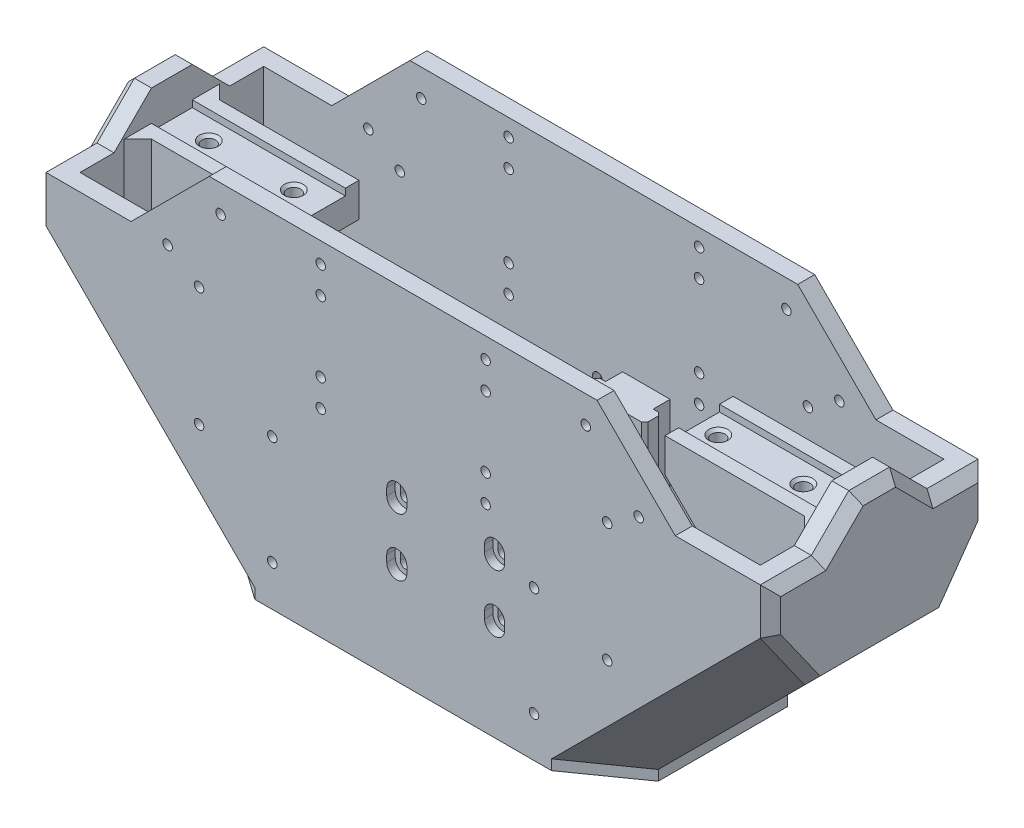
SolidWorks part; units mm, degrees
ref_plane "Front Plane" through (0, 0, 0) normal (0, 0, 1) x (1, 0, 0)
ref_plane "Top Plane" through (0, 0, 0) normal (0, 1, 0) x (1, 0, 0)
ref_plane "Right Plane" through (0, 0, 0) normal (1, 0, 0) x (0, 0, -1)
sketch "Sketch1" plane through (0, 0, 0) normal (0, 1, 0) x (1, 0, 0)
  line L1 (-100, -27) -> (100, -27)
  line L2 (-100, -27) -> (-100, 27)
  line L3 (-100, 27) -> (100, 27)
  line L4 (100, -27) -> (100, 27)
  line L5 (-100, -27) -> (100, 27) construction
  line L6 (-100, 27) -> (100, -27) construction
  point P0 (0, 0)
  dimension "D1" = 200
  dimension "D2" = 54
extrude "Boss-Extrude1" add sketch "Sketch1" along normal blind 70
shell "Shell1" thickness 5
sketch "Sketch2" plane through (105, 0, 0) normal (1, 0, 0) x (0, 0, -1)
  line L0 (-17, 70) -> (-6, 81)
  line L1 (-32, 70) -> (32, 70) construction
  line L2 (-6, 81) -> (6, 81)
  line L3 (6, 81) -> (17, 70)
  line L4 (17, 70) -> (-17, 70)
  line L5 (0, 81) -> (0, 75) construction
  dimension "D1" = 11
  dimension "D2" = 45
  dimension "D3" = 45
  dimension "D4" = 12
extrude "Boss-Extrude2" add sketch "Sketch2" against normal blind 5
sketch "Sketch4" plane through (0, 0, -32) normal (0, 0, -1) x (-1, 0, 0)
  line L0 (-80, 70) -> (-57, 93)
  line L1 (-105, 70) -> (105, 70) construction
  line L2 (-57, 93) -> (57, 93)
  line L3 (57, 93) -> (80, 70)
  line L4 (80, 70) -> (-80, 70)
  line L5 (0, 93) -> (0, 70) construction
  line L6 (-105, 70) -> (-105, -5) construction
  dimension "D1" = 23
  dimension "D2" = 25
  dimension "D3" = 45
extrude "Boss-Extrude3" add sketch "Sketch4" against normal blind 5
sketch "Sketch3" plane through (0, 0, -32) normal (0, 0, -1) x (-1, 0, 0)
  line L1 (-28, 56) -> (28, 56) construction
  line L2 (-28, 56) -> (-28, 88) construction
  line L3 (-28, 88) -> (28, 88) construction
  line L4 (28, 56) -> (28, 88) construction
  line L5 (-28, 56) -> (28, 88) construction
  line L6 (-28, 88) -> (28, 56) construction
  line L7 (57, 93) -> (-57, 93) construction
  circle A0 centre (-28, 88) radius 1.4
  circle A1 centre (-28, 56) radius 1.4
  circle A2 centre (28, 88) radius 1.4
  circle A3 centre (28, 56) radius 1.4
  point P0 (0, 72)
  dimension "D1" = 2.8
  dimension "D2" = 56
  dimension "D3" = 32
  dimension "D4" = 5
extrude "Cut-Extrude1" cut sketch "Sketch3" against normal blind 6
mirror "Mirror4" about plane through (0, 0, 0) normal (0, 0, 1) of "Boss-Extrude3"
mirror "Mirror5" about plane through (0, 0, 0) normal (1, 0, 0) of "Boss-Extrude2"
sketch "Sketch5" plane through (0, 0, 0) normal (0, 0, 1) x (1, 0, 0)
  line L0 (-100, 70) -> (-55, 70)
  line L1 (-55, 70) -> (-55, 62)
  line L2 (-55, 62) -> (-100, 17)
  line L4 (-100, 17) -> (-100, 70)
  line L5 (-100, 81) -> (-100, 70) construction
  line L6 (-105, 70) -> (-80, 70) construction
  dimension "D1" = 45
  dimension "D2" = 8
  dimension "D3" = 45
extrude "Boss-Extrude4" add sketch "Sketch5" along normal mid plane 20
sketch "Sketch9" plane through (0, 70, 0) normal (0, 1, 0) x (1, 0, 0)
  line L4 (-55, 10) -> (-100, 10)
  line L5 (-100, 10) -> (-100, -10)
  line L6 (-100, -10) -> (-55, -10)
  line L7 (-55, -10) -> (-55, 10)
  line L8 (-55, 10) -> (-100, 10)
  line L10 (-100, -10) -> (-55, -10)
  line L11 (-55, -10) -> (-55, 10)
  line L13 (-100, 10) -> (-100, -10)
  dimension "D1" = 0
extrude "Boss-Extrude6" add sketch "Sketch9" along normal blind 2
sketch "Sketch10" plane through (-100, 0, 0) normal (1, 0, 0) x (0, 0, -1)
  line L0 (-10, 72) -> (10, 72) construction
  line L1 (-6, 72) -> (6, 72)
  line L2 (-6, 72) -> (-6, 70)
  line L3 (-6, 70) -> (6, 70)
  line L4 (6, 72) -> (6, 70)
  line L5 (-6, 72) -> (6, 70) construction
  line L6 (-6, 70) -> (6, 72) construction
  point P0 (0, 71)
  dimension "D1" = 2
  dimension "D2" = 12
extrude "Cut-Extrude2" cut sketch "Sketch10" along normal up to next
mirror "Mirror24" about plane through (0, 0, 0) normal (1, 0, 0) of "Boss-Extrude6", "Boss-Extrude4", "Cut-Extrude2"
chamfer "Chamfer3" distance 40 angle 45 2 edges at (100, 0, 0) (-100, 0, 0)
chamfer "Chamfer5" distance 43 angle 45 2 edges at (105, -5, 0) (-105, -5, 0)
chamfer "Chamfer11" distance 10 angle 45 4 edges at (80, 20, 27) (80, 20, -27) (-80, 20, -27) (-80, 20, 27)
chamfer "Chamfer12" distance 13 angle 45 4 edges at (83.5, 16.5, -32) (83.5, 16.5, 32) (-83.5, 16.5, -32) (-83.5, 16.5, 32)
chamfer "Chamfer13" distance 4 angle 45 4 edges at (-100, 56, 10) (-100, 56, -10) (100, 56, -10) (100, 56, 10)
sketch "Sketch16" plane through (105, 0, 0) normal (1, 0, 0) x (0, 0, -1)
  line L10 (-19, 38) -> (19, 38)
  line L11 (19, 38) -> (32, 56.3848)
  line L12 (32, 56.3848) -> (32, 70)
  line L13 (32, 70) -> (17, 70)
  line L14 (17, 70) -> (6, 81)
  line L15 (6, 81) -> (-6, 81)
  line L16 (-6, 81) -> (-17, 70)
  line L17 (-17, 70) -> (-32, 70)
  line L18 (-32, 70) -> (-32, 56.3848)
  line L19 (-32, 56.3848) -> (-19, 38)
  line L20 (-19, 38) -> (19, 38)
  line L21 (19, 38) -> (32, 56.3848)
  line L22 (32, 56.3848) -> (32, 70)
  line L23 (32, 70) -> (17, 70)
  line L24 (17, 70) -> (6, 81)
  line L25 (6, 81) -> (-6, 81)
  line L26 (-6, 81) -> (-17, 70)
  line L27 (-17, 70) -> (-32, 70)
  line L28 (-32, 70) -> (-32, 56.3848)
  line L29 (-32, 56.3848) -> (-19, 38)
  dimension "D1" = 0
extrude "Boss-Extrude10" add sketch "Sketch16" along normal blind 3
chamfer "Chamfer14" distance 3 angle 45 10 edges at (108, 63.1924, 32) (108, 70, 24.5) (108, 75.5, 11.5) (108, 81, 0) (108, 75.5, -11.5) (108, 70, -24.5) (108, 63.1924, -32) (108, 47.1924, -25.5) (108, 38, 0) (108, 47.1924, 25.5)
mirror "Mirror28" about plane through (0, 0, 0) normal (1, 0, 0) of "Chamfer14", "Boss-Extrude10"
sketch "Sketch17" plane through (0, 0, 0) normal (0, 1, 0) x (1, 0, 0)
  line L0 (-57, -27) -> (57, -27) construction
  line L1 (5.5, -27) -> (19.5, -27)
  line L2 (5.5, -27) -> (5.5, -22)
  line L3 (5.5, -22) -> (19.5, -22)
  line L4 (19.5, -27) -> (19.5, -22)
  line L5 (5.5, -27) -> (19.5, -22) construction
  line L6 (5.5, -22) -> (19.5, -27) construction
  line L7 (3, -22) -> (22, -22)
  line L8 (3, -22) -> (3, -17)
  line L9 (3, -17) -> (22, -17)
  line L10 (22, -22) -> (22, -17)
  line L11 (3, -22) -> (22, -17) construction
  line L12 (3, -17) -> (22, -22) construction
  point P0 (12.5, -24.5)
  point P5 (12.5, -19.5)
  line M10 (-45.8579, -27) -> (45.8579, -27)
  dimension "D1" = 19
  dimension "D2" = 14
  dimension "D3" = 5
  dimension "D4" = 12.5
extrude "Boss-Extrude11" add sketch "Sketch17" along normal blind 45 contours L7 L10 L9 L8 L3 | L4 L3 L2 M10
sketch "Sketch20" plane through (0, 0, 0) normal (0, 1, 0) x (1, 0, 0)
  line L0 (22, -22) -> (22, -17) construction
  line L1 (3, -17) -> (22, -17)
  line L2 (3, -17) -> (3, -12)
  line L3 (3, -12) -> (22, -12)
  line L4 (22, -17) -> (22, -12)
  dimension "D1" = 5
extrude "Boss-Extrude14" add sketch "Sketch20" along normal blind 8
mirror "Mirror29" about plane through (0, 0, 0) normal (0, 0, 1) of "Boss-Extrude14", "Boss-Extrude11"
sketch "Sketch22" plane through (0, 0, -27) normal (0, 0, 1) x (1, 0, 0)
  line L0 (5.5, 0) -> (-45.8579, 0) construction
  line L1 (-1.875, 21.8) -> (26.875, 21.8) construction
  line L2 (-1.875, 21.8) -> (-1.875, 38.8) construction
  line L3 (-1.875, 38.8) -> (26.875, 38.8) construction
  line L4 (26.875, 21.8) -> (26.875, 38.8) construction
  line L5 (-1.875, 21.8) -> (26.875, 38.8) construction
  line L6 (-1.875, 38.8) -> (26.875, 21.8) construction
  line L7 (3, 45) -> (22, 45) construction
  line L8 (-1.875, 37.8) -> (-1.875, 39.8) construction
  line L9 (-3.325, 37.8) -> (-3.325, 39.8)
  line L10 (-0.425, 37.8) -> (-0.425, 39.8)
  line L11 (12.5, 38.8) -> (12.5, 30.3) construction
  line L12 (12.5, 30.3) -> (-1.875, 30.3) construction
  line L13 (26.875, 37.8) -> (26.875, 39.8) construction
  line L14 (28.325, 37.8) -> (28.325, 39.8)
  line L15 (25.425, 37.8) -> (25.425, 39.8)
  line L16 (-1.875, 22.8) -> (-1.875, 20.8) construction
  line L17 (-3.325, 22.8) -> (-3.325, 20.8)
  line L18 (-0.425, 22.8) -> (-0.425, 20.8)
  line L19 (26.875, 22.8) -> (26.875, 20.8) construction
  line L20 (28.325, 22.8) -> (28.325, 20.8)
  line L21 (25.425, 22.8) -> (25.425, 20.8)
  arc A4 (-3.325, 37.8) -> (-0.425, 37.8) centre (-1.875, 37.8) ccw
  arc A5 (-0.425, 39.8) -> (-3.325, 39.8) centre (-1.875, 39.8) ccw
  arc A6 (28.325, 37.8) -> (25.425, 37.8) centre (26.875, 37.8) cw
  arc A7 (25.425, 39.8) -> (28.325, 39.8) centre (26.875, 39.8) cw
  arc A8 (-3.325, 22.8) -> (-0.425, 22.8) centre (-1.875, 22.8) cw
  arc A9 (-0.425, 20.8) -> (-3.325, 20.8) centre (-1.875, 20.8) cw
  arc A10 (28.325, 22.8) -> (25.425, 22.8) centre (26.875, 22.8) ccw
  arc A11 (25.425, 20.8) -> (28.325, 20.8) centre (26.875, 20.8) ccw
  point P0 (12.5, 30.3)
  point P7 (12.5, 45)
  point P11 (-1.875, 38.8)
  point P22 (26.875, 38.8)
  point P29 (-1.875, 21.8)
  point P36 (26.875, 21.8)
  dimension "D4" = 1.45
  dimension "D1" = 21.8
  dimension "D2" = 28.75
  dimension "D3" = 17
  dimension "D5" = 2
extrude "Cut-Extrude4" cut sketch "Sketch22" against normal blind 2.5
sketch "Sketch23" plane through (0, 0, -29.5) normal (0, 0, 1) x (1, 0, 0)
  line L6 (29.825, 37.8) -> (29.825, 39.8)
  line L7 (23.925, 39.8) -> (23.925, 37.8)
  line L8 (29.825, 37.8) -> (29.825, 39.8)
  line L9 (23.925, 39.8) -> (23.925, 37.8)
  line L12 (1.075, 37.8) -> (1.075, 39.8)
  line L13 (-4.825, 39.8) -> (-4.825, 37.8)
  line L14 (1.075, 37.8) -> (1.075, 39.8)
  line L15 (-4.825, 39.8) -> (-4.825, 37.8)
  line L18 (-4.825, 22.8) -> (-4.825, 20.8)
  line L19 (1.075, 20.8) -> (1.075, 22.8)
  line L20 (-4.825, 22.8) -> (-4.825, 20.8)
  line L21 (1.075, 20.8) -> (1.075, 22.8)
  line L24 (23.925, 22.8) -> (23.925, 20.8)
  line L25 (29.825, 20.8) -> (29.825, 22.8)
  line L26 (23.925, 22.8) -> (23.925, 20.8)
  line L27 (29.825, 20.8) -> (29.825, 22.8)
  arc A6 (23.925, 37.8) -> (29.825, 37.8) centre (26.875, 37.8) ccw
  arc A7 (29.825, 39.8) -> (23.925, 39.8) centre (26.875, 39.8) ccw
  arc A8 (23.925, 37.8) -> (29.825, 37.8) centre (26.875, 37.8) ccw
  arc A9 (29.825, 39.8) -> (23.925, 39.8) centre (26.875, 39.8) ccw
  arc A12 (-4.825, 37.8) -> (1.075, 37.8) centre (-1.875, 37.8) ccw
  arc A13 (1.075, 39.8) -> (-4.825, 39.8) centre (-1.875, 39.8) ccw
  arc A14 (-4.825, 37.8) -> (1.075, 37.8) centre (-1.875, 37.8) ccw
  arc A15 (1.075, 39.8) -> (-4.825, 39.8) centre (-1.875, 39.8) ccw
  arc A18 (1.075, 22.8) -> (-4.825, 22.8) centre (-1.875, 22.8) ccw
  arc A19 (-4.825, 20.8) -> (1.075, 20.8) centre (-1.875, 20.8) ccw
  arc A20 (1.075, 22.8) -> (-4.825, 22.8) centre (-1.875, 22.8) ccw
  arc A21 (-4.825, 20.8) -> (1.075, 20.8) centre (-1.875, 20.8) ccw
  arc A24 (29.825, 22.8) -> (23.925, 22.8) centre (26.875, 22.8) ccw
  arc A25 (23.925, 20.8) -> (29.825, 20.8) centre (26.875, 20.8) ccw
  arc A26 (29.825, 22.8) -> (23.925, 22.8) centre (26.875, 22.8) ccw
  arc A27 (23.925, 20.8) -> (29.825, 20.8) centre (26.875, 20.8) ccw
  dimension "D1" = 1.5
  dimension "D2" = 1.5
  dimension "D3" = 1.5
  dimension "D4" = 1.5
extrude "Cut-Extrude5" cut sketch "Sketch23" against normal up to next contours A8 L8 A9 L9 | A14 L14 A15 L15 | A20 L20 A21 L21 | A26 L26 A27 L27
mirror "Mirror30" about plane through (0, 0, 0) normal (0, 0, 1) of "Cut-Extrude5", "Cut-Extrude4"
sketch "Sketch24" plane through (30, -30, 0) normal (-0.7071, 0.7071, 0) x (0, 0, 1)
  line L0 (17, 42.4264) -> (-17, 42.4264) construction
  line L1 (-7.5, 47.4264) -> (7.5, 47.4264)
  line L2 (-7.5, 47.4264) -> (-7.5, 55.4264)
  line L3 (-7.5, 55.4264) -> (7.5, 55.4264)
  line L4 (7.5, 47.4264) -> (7.5, 55.4264)
  line L5 (-7.5, 47.4264) -> (7.5, 55.4264) construction
  line L6 (-7.5, 55.4264) -> (7.5, 47.4264) construction
  point P0 (0, 51.4264)
  dimension "D1" = 5
  dimension "D2" = 15
  dimension "D3" = 8
extrude "Cut-Extrude6" cut sketch "Sketch24" against normal up to next
chamfer "Chamfer18" distance 4 angle 45 4 edges at (22, 0, 17) (3, 0, -17) (3, 0, 17) (22, 0, -17)
chamfer "Chamfer19" distance 1 angle 45 8 edges at (3, 24.5, 22) (22, 24.5, 22) (22, 26.5, 17) (3, 26.5, 17) (3, 24.5, -22) (3, 26.5, -17) (22, 26.5, -17) (22, 24.5, -22)
chamfer "Chamfer20" distance 2 angle 45 4 edges at (65.2855, 1.7855, -7.5) (65.2855, 1.7855, 7.5) (70.9424, 7.4424, 7.5) (70.9424, 7.4424, -7.5)
sketch "Sketch25" plane through (0, -5, 0) normal (0, -1, 0) x (1, 0, 0)
  line L8 (-43.6152, -32) -> (43.6152, -32)
  line L9 (43.6152, -32) -> (62, -19)
  line L10 (62, -19) -> (62, 19)
  line L11 (62, 19) -> (43.6152, 32)
  line L12 (43.6152, 32) -> (-43.6152, 32)
  line L13 (-43.6152, 32) -> (-62, 19)
  line L14 (-62, 19) -> (-62, -19)
  line L15 (-62, -19) -> (-43.6152, -32)
  line L16 (-43.6152, -32) -> (43.6152, -32)
  line L17 (43.6152, -32) -> (62, -19)
  line L18 (62, -19) -> (62, 19)
  line L19 (62, 19) -> (43.6152, 32)
  line L20 (43.6152, 32) -> (-43.6152, 32)
  line L21 (-43.6152, 32) -> (-62, 19)
  line L22 (-62, 19) -> (-62, -19)
  line L23 (-62, -19) -> (-43.6152, -32)
  dimension "D1" = 0
extrude "Boss-Extrude15" add sketch "Sketch25" along normal blind 3
sketch "Sketch27" plane through (0, 0, 0) normal (0, 1, 0) x (1, 0, 0)
  line L0 (26, 12) -> (-1, 12) construction
  line L1 (-30, -12) -> (30, -12)
  line L2 (-30, -12) -> (-30, 12)
  line L3 (-30, 12) -> (30, 12)
  line L4 (30, -12) -> (30, 12)
  line L5 (22, -12) -> (3, -12) construction
  line L6 (-30, 12) -> (30, -12) construction
  point P8 (0, 0)
  dimension "D1" = 60
extrude "Cut-Extrude7" cut sketch "Sketch27" against normal up to next
chamfer "Chamfer21" distance 5 angle 45 4 edges at (-30, -4, -12) (30, -4, -12) (30, -4, 12) (-30, -4, 12)
sketch "Sketch28" plane through (0, -8, 0) normal (0, -1, 0) x (1, 0, 0)
  line L0 (62, 19) -> (43.6152, 32) construction
  line L1 (-52.8076, -25.5) -> (52.8076, -25.5) construction
  line L2 (-52.8076, -25.5) -> (-52.8076, 25.5) construction
  line L3 (-52.8076, 25.5) -> (52.8076, 25.5) construction
  line L4 (52.8076, -25.5) -> (52.8076, 25.5) construction
  line L5 (-52.8076, -25.5) -> (52.8076, 25.5) construction
  line L6 (-52.8076, 25.5) -> (52.8076, -25.5) construction
  circle A0 centre (-52.8076, 0) radius 2.75
  circle A1 centre (-52.8076, 15) radius 2.75
  circle A2 centre (-52.8076, -15) radius 2.75
  point P0 (0, 0)
  dimension "D1" = 5.5
  dimension "D2" = 15
  dimension "D3" = 15
extrude "Cut-Extrude8" cut sketch "Sketch28" against normal blind 7
mirror "Mirror31" about plane through (0, 0, 0) normal (1, 0, 0) of "Cut-Extrude8"
sketch "Sketch29" plane through (0, -8, 0) normal (0, -1, 0) x (1, 0, 0)
  line L0 (-54.9289, 24) -> (54.9289, 24) construction
  line L3 (43.6152, 32) -> (-43.6152, 32) construction
  line L4 (-43.6152, 32) -> (-62, 19) construction
  line L5 (62, 19) -> (43.6152, 32) construction
  circle A1 centre (0, 24) radius 2.75
  circle A2 centre (20, 24) radius 2.75
  circle A3 centre (40, 24) radius 2.75
  dimension "D1" = 5.5
  dimension "D3" = 20
  dimension "D4" = 8
  dimension "D2" = 3
extrude "Cut-Extrude9" cut sketch "Sketch29" against normal blind 7
mirror "Mirror32" about plane through (0, 0, 0) normal (1, 0, 0) of "Cut-Extrude9"
mirror "Mirror33" about plane through (0, 0, 0) normal (0, 0, 1) of "Mirror32", "Cut-Extrude9"
sketch "Sketch32" plane through (0, -1, 0) normal (0, -1, 0) x (1, 0, 0)
  circle A0 centre (-40, 24) radius 1.9
  circle A1 centre (-52.8076, 15) radius 1.9
  circle A2 centre (-52.8076, 0) radius 1.9
  dimension "D1" = 3.8
extrude "Cut-Extrude11" cut sketch "Sketch32" against normal blind 2
mirror "Mirror34" about plane through (0, 0, 0) normal (0, 0, 1) of "Cut-Extrude11"
mirror "Mirror35" about plane through (0, 0, 0) normal (1, 0, 0) of "Mirror34", "Cut-Extrude11"
sketch "Sketch33" plane through (0, 70, 0) normal (0, 1, 0) x (1, 0, 0)
  line L0 (-100, -6) -> (-100, 6) construction
  circle A0 centre (-89.15, 0) radius 2
  circle A1 centre (-64.15, 0) radius 2
  dimension "D1" = 25
  dimension "D2" = 10.85
  dimension "D3" = 4
extrude "Cut-Extrude12" cut sketch "Sketch33" against normal blind 5.2
sketch "Sketch34" plane through (0, 70, 0) normal (0, 1, 0) x (1, 0, 0)
  line L0 (100, 6) -> (100, -6) construction
  circle A0 centre (85.65, 0) radius 2
  circle A1 centre (60.65, 0) radius 2
  dimension "D1" = 4
  dimension "D2" = 25
  dimension "D3" = 14.35
extrude "Cut-Extrude13" cut sketch "Sketch34" against normal blind 5.2
sketch "Sketch35" plane through (0, 64.8, 0) normal (0, 1, 0) x (1, 0, 0)
  circle A0 centre (-89.15, 0) radius 1.4
  circle A1 centre (-64.15, 0) radius 1.4
  circle A2 centre (60.65, 0) radius 1.4
  circle A3 centre (85.65, 0) radius 1.4
  dimension "D1" = 2.8
extrude "Cut-Extrude14" cut sketch "Sketch35" against normal blind 6
pattern_linear "LPattern1" count 2 spacing 8 along (0, -1, 0) of "Cut-Extrude1"
sketch "Sketch36" plane through (0, 0, 32) normal (0, 0, 1) x (1, 0, 0)
  line L0 (-57, 93) -> (57, 93) construction
  line L1 (-24.25, 58.3) -> (24.25, 58.3) construction
  line L2 (-24.25, 58.3) -> (-24.25, 87) construction
  line L3 (-24.25, 87) -> (24.25, 87) construction
  line L4 (24.25, 58.3) -> (24.25, 87) construction
  line L5 (-24.25, 58.3) -> (24.25, 87) construction
  line L6 (-24.25, 87) -> (24.25, 58.3) construction
  circle A0 centre (-24.25, 87) radius 1.4
  circle A1 centre (24.25, 87) radius 1.4
  circle A2 centre (24.25, 58.3) radius 1.4
  circle A3 centre (-24.25, 58.3) radius 1.4
  point P0 (0, 72.65)
  dimension "D1" = 2.8
  dimension "D2" = 48.5
  dimension "D3" = 28.7
  dimension "D4" = 6
extrude "Cut-Extrude15" cut sketch "Sketch36" against normal up to next
pattern_linear "LPattern2" count 2 spacing 8 along (0, -1, 0) of "Cut-Extrude15"
sketch "Sketch39" plane through (0, 0, -32) normal (0, 0, -1) x (-1, 0, 0)
  line L0 (-105, 56.3848) -> (-43.6152, -5) construction
  line L1 (-38.4731, 4) -> (38.4731, 4) construction
  line L2 (-38.4731, 4) -> (-38.4731, 36) construction
  line L3 (-38.4731, 36) -> (38.4731, 36) construction
  line L4 (38.4731, 4) -> (38.4731, 36) construction
  line L5 (-38.4731, 4) -> (38.4731, 36) construction
  line L6 (-38.4731, 36) -> (38.4731, 4) construction
  line L8 (43.6152, -8) -> (-43.6152, -8) construction
  circle A0 centre (-38.4731, 4) radius 1.4
  circle A1 centre (38.4731, 4) radius 1.4
  circle A2 centre (38.4731, 36) radius 1.4
  circle A3 centre (-38.4731, 36) radius 1.4
  point P0 (0, 20)
  dimension "D4" = 2.8
  dimension "D1" = 10
  dimension "D2" = 12
  dimension "D3" = 32
extrude "Cut-Extrude16" cut sketch "Sketch39" against normal up to next
sketch "Sketch40" plane through (0, 0, -32) normal (0, 0, -1) x (-1, 0, 0)
  line L1 (-60, 28.3553) -> (60, 28.3553) construction
  line L2 (-60, 28.3553) -> (-60, 63.3553) construction
  line L3 (-60, 63.3553) -> (60, 63.3553) construction
  line L4 (60, 28.3553) -> (60, 63.3553) construction
  line L5 (-60, 28.3553) -> (60, 63.3553) construction
  line L6 (-60, 63.3553) -> (60, 28.3553) construction
  line L9 (43.6152, -5) -> (105, 56.3848) construction
  circle A0 centre (-60, 63.3553) radius 1.4
  circle A1 centre (60, 63.3553) radius 1.4
  circle A2 centre (60, 28.3553) radius 1.4
  circle A3 centre (-60, 28.3553) radius 1.4
  point P0 (0, 45.8553)
  dimension "D4" = 2.8
  dimension "D3" = 12
  dimension "D1" = 120
  dimension "D2" = 35
extrude "Cut-Extrude17" cut sketch "Sketch40" against normal up to next
mirror "Mirror36" about plane through (0, 0, 0) normal (0, 0, 1) of "Cut-Extrude16", "Cut-Extrude17"
sketch "Sketch41" plane through (0, 0, -32) normal (0, 0, -1) x (-1, 0, 0)
  line L0 (-53.6863, 85) -> (-69.2426, 69.4437) construction
  line L2 (-57, 93) -> (-80, 70) construction
  line L4 (57, 93) -> (-57, 93) construction
  circle A1 centre (-69.2426, 69.4437) radius 1.4
  circle A2 centre (-53.6863, 85) radius 1.4
  dimension "D2" = 2.8
  dimension "D3" = 22
  dimension "D4" = 8
  dimension "D1" = 8
extrude "Cut-Extrude18" cut sketch "Sketch41" against normal up to next
mirror "Mirror37" about plane through (0, 0, 0) normal (1, 0, 0) of "Cut-Extrude18"
mirror "Mirror38" about plane through (0, 0, 0) normal (0, 0, 1) of "Mirror37", "Cut-Extrude18"
sketch "Sketch43" plane through (-33.5, -33.5, 0) normal (-0.7071, -0.7071, 0) x (0, 0, 1)
  line L1 (-12, 49.7107) -> (12, 49.7107) construction
  line L2 (-12, 49.7107) -> (-12, 91.7107) construction
  line L3 (-12, 91.7107) -> (12, 91.7107) construction
  line L4 (12, 49.7107) -> (12, 91.7107) construction
  line L5 (-12, 49.7107) -> (12, 91.7107) construction
  line L6 (-12, 91.7107) -> (12, 49.7107) construction
  line L10 (-19, 101.1163) -> (-19, 40.3051) construction
  circle A0 centre (-12, 91.7107) radius 1.4
  circle A1 centre (12, 91.7107) radius 1.4
  circle A2 centre (12, 49.7107) radius 1.4
  circle A3 centre (-12, 49.7107) radius 1.4
  point P0 (0, 70.7107)
  point P6 (-19, 70.7107)
  dimension "D3" = 2.8
  dimension "D1" = 42
  dimension "D2" = 24
extrude "Cut-Extrude19" cut sketch "Sketch43" against normal up to next
chamfer "Chamfer22" distance 0.8 angle 45 4 edges at (85.65, 70, 2) (60.65, 70, 2) (-64.15, 70, 2) (-89.15, 70, 2)
chamfer "Chamfer23" distance 1 angle 45 16 edges at (-20, -8, 21.25) (0, -8, 21.25) (-40, -8, 21.25) (-52.8076, -8, 12.25) (-52.8076, -8, -2.75) (-52.8076, -8, -17.75) (-40, -8, -21.25) (-20, -8, -21.25) (0, -8, -21.25) (20, -8, 21.25) (40, -8, 21.25) (52.8076, -8, 12.25) (52.8076, -8, -2.75) (20, -8, -21.25) (40, -8, -21.25) (52.8076, -8, -17.75)
